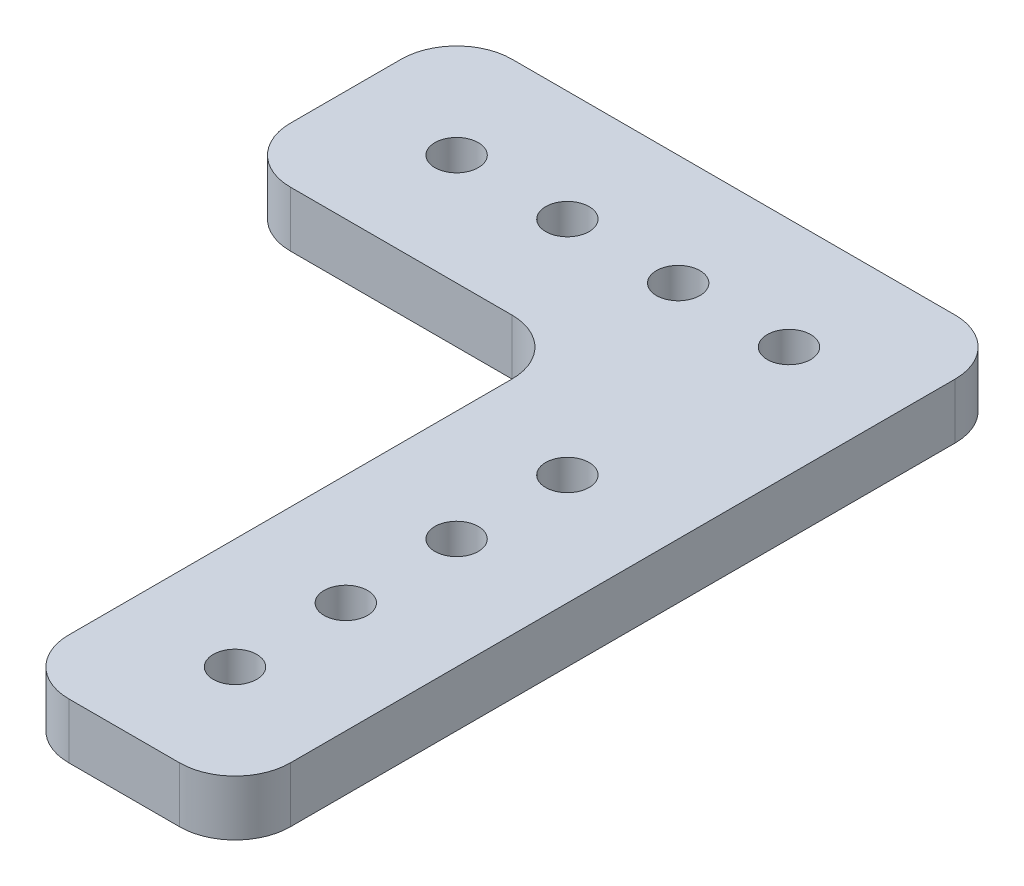
SolidWorks part; units mm, degrees
material "6061-T6 (SS)"
ref_plane "Front Plane" through (0, 0, 0) normal (0, 0, 1) x (1, 0, 0)
ref_plane "Top Plane" through (0, 0, 0) normal (0, 1, 0) x (1, 0, 0)
ref_plane "Right Plane" through (0, 0, 0) normal (1, 0, 0) x (0, 0, -1)
sketch "Sketch1" plane through (0, 0, 0) normal (0, 1, 0) x (1, 0, 0)
  line L0 (-38.1, 76.2) -> (25.4, 76.2) construction
  line L1 (0, 0) -> (25.4, 0)
  line L2 (0, 0) -> (0, 88.9)
  line L3 (0, 88.9) -> (25.4, 88.9)
  line L4 (25.4, 0) -> (25.4, 88.9)
  line L5 (25.4, 88.9) -> (-38.1, 88.9)
  line L6 (25.4, 88.9) -> (25.4, 63.5)
  line L7 (25.4, 63.5) -> (-38.1, 63.5)
  line L8 (-38.1, 88.9) -> (-38.1, 63.5)
  line L9 (12.7, 0) -> (12.7, 88.9) construction
  circle A0 centre (12.7, 76.2) radius 2.4892
  circle A1 centre (-25.4, 76.2) radius 2.4892
  circle A2 centre (-12.7, 76.2) radius 2.4892
  circle A3 centre (0, 76.2) radius 2.4892
  circle A4 centre (12.7, 50.8) radius 2.4892
  circle A5 centre (12.7, 38.1) radius 2.4892
  circle A6 centre (12.7, 25.4) radius 2.4892
  circle A7 centre (12.7, 12.7) radius 2.4892
  dimension "D6" = 4.9784
  dimension "D7" = 12.7
  dimension "D8" = 12.7
  dimension "D9" = 12.7
  dimension "D10" = 12.7
  dimension "D11" = 12.7
  dimension "D12" = 12.7
  dimension "D13" = 12.7
  dimension "D1" = 25.4
  dimension "D2" = 25.4
  dimension "D3" = 88.9
  dimension "D4" = 63.5
  dimension "D5" = 12.7
extrude "Boss-Extrude1" add sketch "Sketch1" along normal blind 6.35 contours A3 L2 L5 L8 L7 A2 A1 | A3 L2 L7 L4 L3 A0 | L4 L7 L2 L1 A7 A6 A5 A4 region at (12.7, 0, -31.75) region at (-19.2405, 0, -76.2) region at (0.3592, 0, -68.6054)
fillet "Fillet1" radius 6.35 6 edges at (0, 3.175, 0) (0, 3.175, -63.5) (-38.1, 3.175, -63.5) (-38.1, 3.175, -88.9) (25.4, 3.175, -88.9) (25.4, 3.175, 0)
